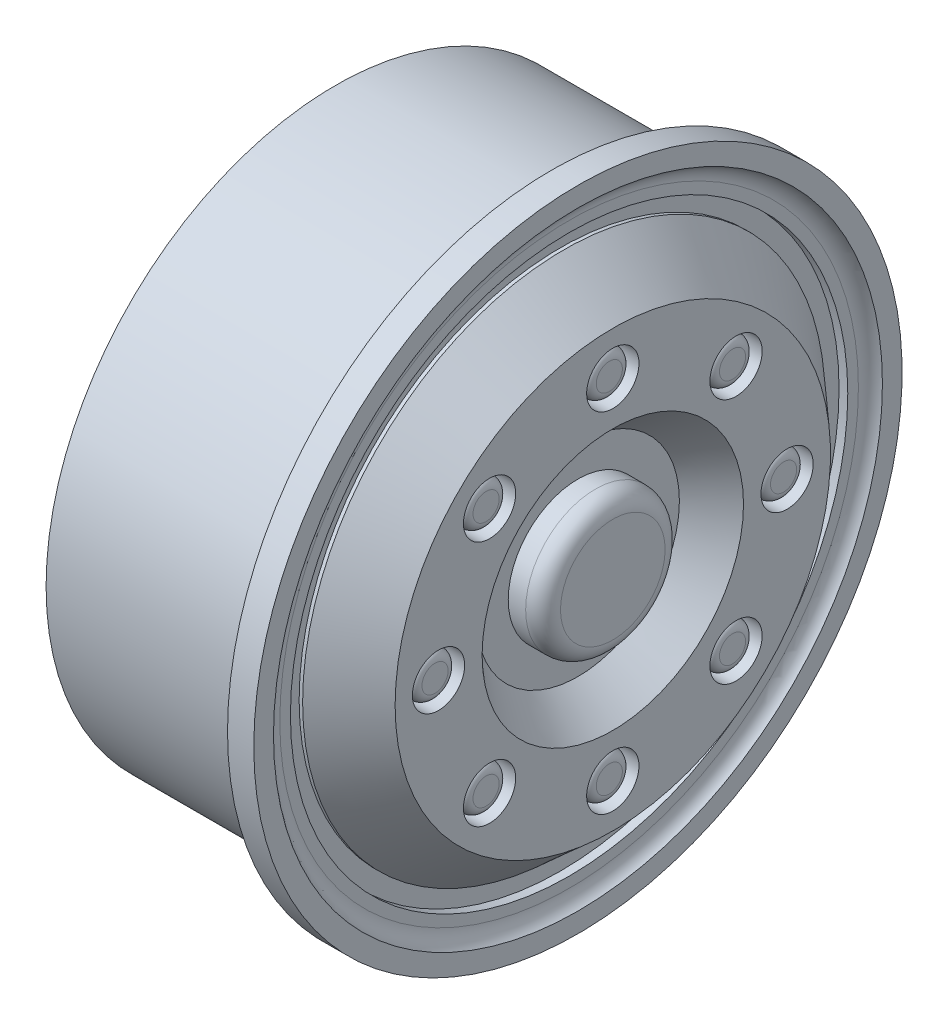
SolidWorks part; units mm, degrees
ref_plane "Front Plane" through (0, 0, 0) normal (0, 0, 1) x (1, 0, 0)
ref_plane "Top Plane" through (0, 0, 0) normal (0, 1, 0) x (1, 0, 0)
ref_plane "Right Plane" through (0, 0, 0) normal (1, 0, 0) x (0, 0, -1)
sketch "Sketch1" plane through (0, 0, 0) normal (0, 0, 1) x (1, 0, 0)
  line L0 (-25, 0) -> (25, 0) construction
  line L1 (6.718, 18.6) -> (5.21, 18.6)
  line L2 (5.21, 18.6) -> (5.21, 16.6)
  line L3 (5.21, 16.6) -> (-7.2, 16.6)
  line L4 (-7.2, 16.6) -> (-7.2, 13.6)
  line L9 (6.21, 16.6) -> (6.21, 15.9908)
  line L14 (6.718, 17.4706) -> (6.718, 18.6)
  line L15 (6.21, 15.9908) -> (5.71, 15.9908)
  line L16 (5.71, 15.9908) -> (5.71, 14.9908)
  line L22 (5.71, 14.9908) -> (5.91, 14.9908)
  line L23 (5.91, 14.9908) -> (8.718, 12.4908)
  line L24 (8.718, 12.4908) -> (8.718, 0)
  line L25 (8.718, 0) -> (4.9942, 0)
  line L26 (-7.2, 13.6) -> (2.8639, 13.6)
  line L27 (2.8639, 13.6) -> (4.9942, 11.4697)
  line L28 (4.9942, 11.4697) -> (4.9942, 0)
  arc A0 (6.21, 16.6) -> (6.718, 17.4706) centre (7.21, 16.6) cw
  dimension "D9" = 1
  dimension "D1" = 50
  dimension "D2" = 25
  dimension "D3" = 0.5
  dimension "D4" = 2
  dimension "D5" = 33.2
  dimension "D6" = 12.41
  dimension "D8" = 1
  dimension "D10" = 0.2
  dimension "D11" = 2
  dimension "D12" = 2.5
  dimension "D13" = 3
revolve "Revolve1" add sketch "Sketch1" angle 360 about L0
sketch "Sketch2" plane through (8.718, 0, 0) normal (1, 0, 0) x (0, 0, -1)
  circle A0 centre (0, 0) radius 7.5
  circle A1 centre (0, 0) radius 12.4908
  circle A2 centre (0, 0) radius 12.4908 construction
  circle A3 centre (0, 0) radius 10 construction
  circle A4 centre (0, 10) radius 1.5
  circle A5 centre (7.0711, 7.0711) radius 1.5
  circle A6 centre (10, 0) radius 1.5
  circle A7 centre (7.0711, -7.0711) radius 1.5
  circle A8 centre (0, -10) radius 1.5
  circle A9 centre (-7.0711, -7.0711) radius 1.5
  circle A10 centre (-10, 0) radius 1.5
  circle A11 centre (-7.0711, 7.0711) radius 1.5
  point P24 (0, 0)
  dimension "D2" = 15
  dimension "D3" = 3
  dimension "D5" = 20
  dimension "D1" = 0
  dimension "D4" = 8
extrude "Cut-Extrude1" cut sketch "Sketch2" against normal blind 2
sketch "Sketch3" plane through (6.718, 0, 0) normal (1, 0, 0) x (0, 0, -1)
  circle A1 centre (0, 0) radius 10 construction
  circle A2 centre (0, 10) radius 1.25
  circle A3 centre (7.0711, 7.0711) radius 1.25
  circle A4 centre (10, 0) radius 1.25
  circle A5 centre (7.0711, -7.0711) radius 1.25
  circle A6 centre (0, -10) radius 1.25
  circle A7 centre (-7.0711, -7.0711) radius 1.25
  circle A8 centre (-10, 0) radius 1.25
  circle A9 centre (-7.0711, 7.0711) radius 1.25
  point P23 (0, 0)
  dimension "D2" = 20
  dimension "D3" = 2.5
  dimension "D4" = 8
extrude "Boss-Extrude1" add sketch "Sketch3" along normal blind 1.8
fillet "Fillet2" radius 0.5 10 edges at (6.718, -10, -1.25) (8.518, -10, -1.25) (6.718, -7.0711, -8.3211) (8.518, -7.0711, -8.3211) (8.518, 7.0711, -8.3211) (8.518, -7.0711, 5.8211) (8.518, 0, -11.25) (8.518, 10, -1.25) (8.518, 7.0711, 5.8211) (8.518, 0, 8.75)
chamfer "Chamfer1" distance 2 angle 40 1 edges at (6.718, 0, -7.5) first distance on face at (6.718, 0, -7.5)
sketch "Sketch4" plane through (6.718, 0, 0) normal (1, 0, 0) x (0, 0, -1)
  circle A0 centre (0, 0) radius 4
  dimension "D1" = 8
extrude "Boss-Extrude2" add sketch "Sketch4" along normal up to surface (2 mm away) up to face at (8.718, 10, -1.5)
fillet "Fillet3" radius 1 1 edges at (8.718, 0, 4)
